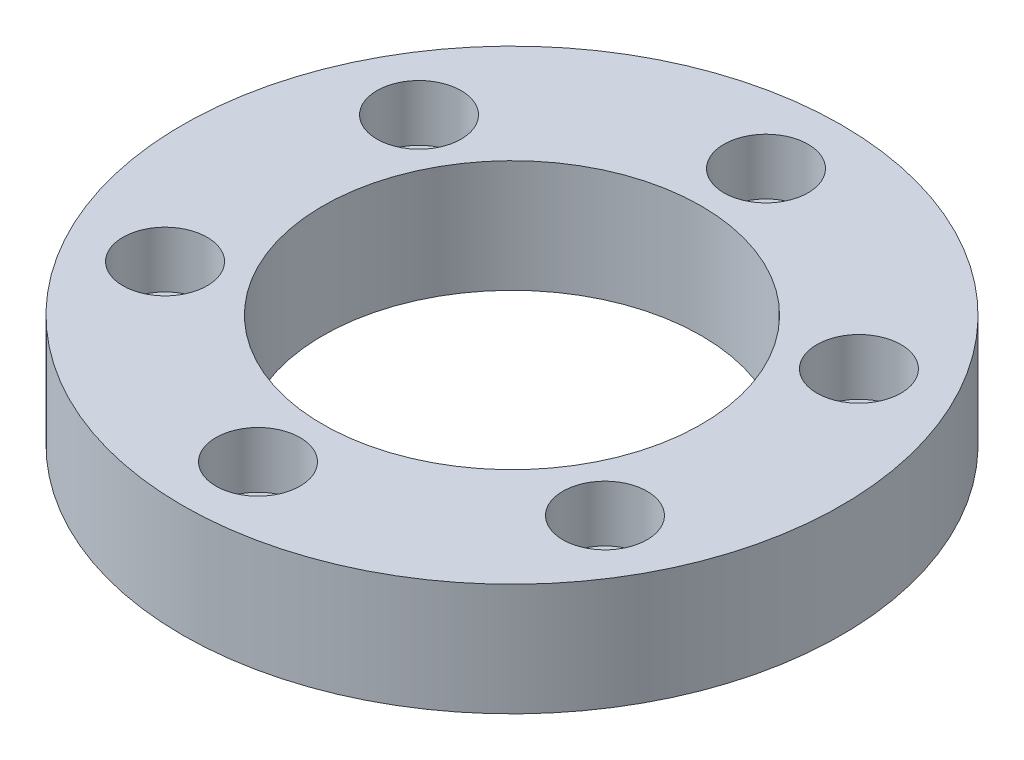
SolidWorks part; units mm, degrees
ref_plane "Front Plane" through (0, 0, 0) normal (0, 0, 1) x (1, 0, 0)
ref_plane "Top Plane" through (0, 0, 0) normal (0, 1, 0) x (1, 0, 0)
ref_plane "Right Plane" through (0, 0, 0) normal (1, 0, 0) x (0, 0, -1)
sketch "Sketch1" plane through (0, 0, 0) normal (1, 0, 0) x (0, 0, -1)
  line L0 (13.485, 8) -> (13.485, 0)
  line L1 (13.485, 0) -> (23.485, 0)
  line L2 (23.485, 0) -> (23.485, 8)
  line L3 (23.485, 8) -> (13.485, 8)
  line L6 (18.1, 8) -> (18.1, 0) construction
  line L7 (0, 0) -> (0, 8) construction
  dimension "D1" = 13.485
  dimension "D2" = 10
  dimension "D3" = 8
  dimension "D5" = 18.1
revolve "Revolve1" add sketch "Sketch1" angle 360 about L7
sketch "Sketch2" plane through (0, 8, 0) normal (0, 1, 0) x (1, 0, 0)
  circle A0 centre (0, 18.1) radius 1.75
  circle A1 centre (0, 18.1) radius 3
  circle A2 centre (0, 0) radius 18.1 construction
  circle A3 centre (15.6751, 9.05) radius 1.75
  circle A4 centre (15.6751, 9.05) radius 3
  circle A5 centre (15.6751, -9.05) radius 1.75
  circle A6 centre (15.6751, -9.05) radius 3
  circle A7 centre (0, -18.1) radius 1.75
  circle A8 centre (0, -18.1) radius 3
  circle A9 centre (-15.6751, -9.05) radius 1.75
  circle A10 centre (-15.6751, -9.05) radius 3
  circle A11 centre (-15.6751, 9.05) radius 1.75
  circle A12 centre (-15.6751, 9.05) radius 3
  point P23 (0, 0)
  dimension "D1" = 36.2
  dimension "D2" = 3.5
  dimension "D3" = 6
  dimension "D4" = 6
extrude "Cut-Extrude1" cut sketch "Sketch2" against normal blind 10 contours A0 | A11 | A9 | A7 | A5 | A3 region at (0, 8, -18.1) region at (15.6751, 8, -9.05) region at (15.6751, 8, 9.05) region at (0, 8, 18.1) region at (-15.6751, 8, 9.05) region at (-15.6751, 8, -9.05)
extrude "Cut-Extrude2" cut sketch "Sketch2<3>" against normal blind 4 contours A12 A11 | A1 A0 | A4 A3 | A10 A9 | A8 A7 | A6 A5 region at (-2.9151, 8, -18.1) region at (12.7599, 8, -9.05) region at (12.7599, 8, 9.05) region at (-2.9151, 8, 18.1) region at (-18.5902, 8, 9.05) region at (-18.5902, 8, -9.05)
sketch "Sketch2<3>" plane through (0, 8, 0) normal (0, 1, 0) x (1, 0, 0) same geometry as "Sketch2"
